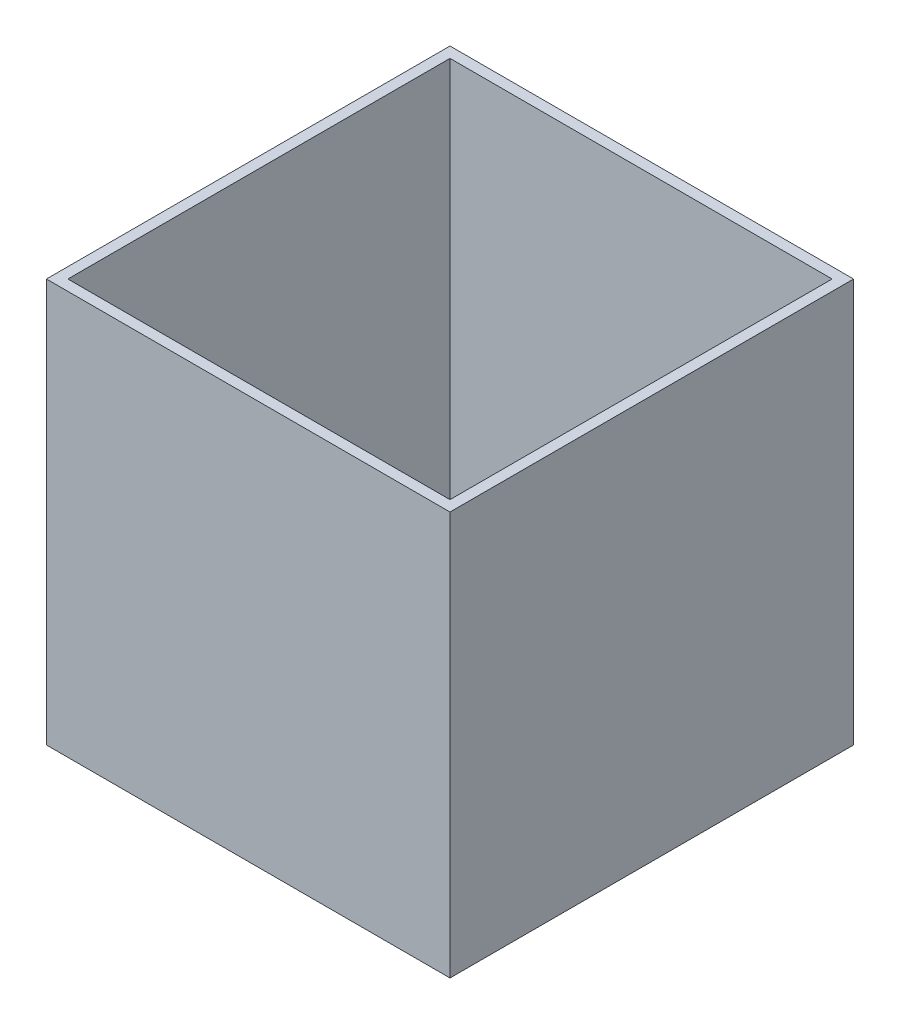
SolidWorks part; units mm, degrees
ref_plane "Front Plane" through (0, 0, 0) normal (0, 0, 1) x (1, 0, 0)
ref_plane "Top Plane" through (0, 0, 0) normal (0, 1, 0) x (1, 0, 0)
ref_plane "Right Plane" through (0, 0, 0) normal (1, 0, 0) x (0, 0, -1)
sketch "Sketch2" plane through (0, 0, 0) normal (0, 1, 0) x (1, 0, 0)
  line L1 (56.5, -56.5) -> (-56.5, -56.5)
  line L2 (56.5, -56.5) -> (56.5, 56.5)
  line L3 (56.5, 56.5) -> (-56.5, 56.5)
  line L4 (-56.5, -56.5) -> (-56.5, 56.5)
  line L5 (56.5, -56.5) -> (-56.5, 56.5) construction
  line L6 (56.5, 56.5) -> (-56.5, -56.5) construction
  point P0 (0, 0)
  dimension "D1" = 113
  dimension "D2" = 113
extrude "Boss-Extrude1" add sketch "Sketch2" along normal blind 113
shell "Shell1" thickness 3 removed face at (0, 113, 0)
